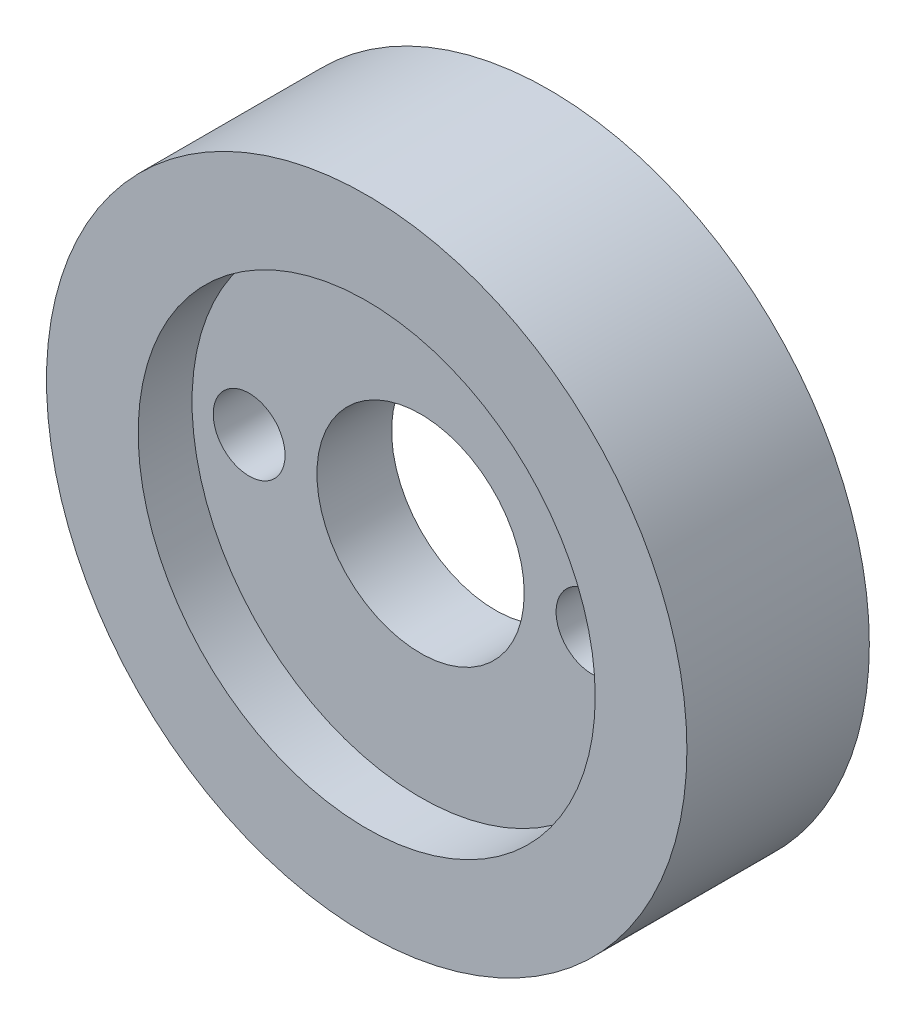
SolidWorks part; units mm, degrees
note: The reader was unsure of these and kept them because the rebuilt part matched: shared geometry of "Sketch2<3>".
ref_plane "Front Plane" through (0, 0, 0) normal (0, 0, 1) x (1, 0, 0)
ref_plane "Top Plane" through (0, 0, 0) normal (0, 1, 0) x (1, 0, 0)
ref_plane "Right Plane" through (0, 0, 0) normal (1, 0, 0) x (0, 0, -1)
sketch "Sketch1" plane through (0, 0, 0) normal (0, 0, 1) x (1, 0, 0)
  circle A0 centre (0, 0) radius 9.8091
  circle A1 centre (0, 0) radius 3.175
  dimension "D1" = 19.6182
  dimension "D2" = 6.35
extrude "Boss-Extrude1" add sketch "Sketch1" along normal mid plane 5.588
sketch "Sketch2" plane through (0, 0, 2.794) normal (0, 0, 1) x (1, 0, 0)
  line L0 (0, 0) -> (0, 1.2313) construction
  line L1 (-7, 0) -> (-3.075, 0)
  circle A0 centre (0, 0) radius 7
  circle A1 centre (0, 0) radius 3.075
  circle A2 centre (-5.2514, 0) radius 1.1
  circle A3 centre (5.2514, 0) radius 1.1
  dimension "D1" = 14
  dimension "D2" = 6.15
  dimension "D3" = 2.2
  dimension "D4" = 10.5029
extrude "Cut-Extrude1" cut sketch "Sketch2" against normal blind 1.65
mirror "Mirror1" about plane through (0, 0, 0) normal (0, 0, 1) of "Cut-Extrude1"
extrude "Cut-Extrude2" cut sketch "Sketch2<3>" against normal through all contours L1 A2 | L1 A2 | A3
sketch "Sketch2<3>" plane through (0, 0, 2.794) normal (0, 0, 1) x (1, 0, 0) same geometry as "Sketch2"
